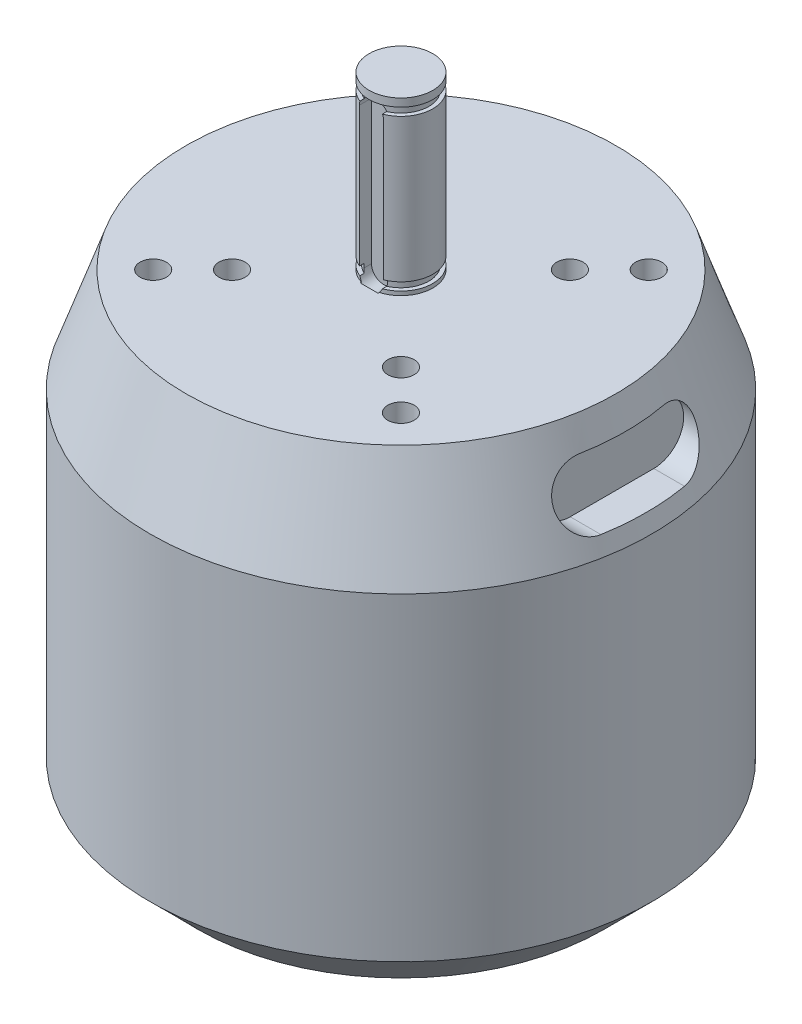
SolidWorks part; units mm, degrees
note: '?' marks a value the reader was unsure of.
ref_plane "정면" through (0, 0, 0) normal (0, 0, 1) x (1, 0, 0)
ref_plane "윗면" through (0, 0, 0) normal (0, 1, 0) x (1, 0, 0)
ref_plane "우측면" through (0, 0, 0) normal (1, 0, 0) x (0, 0, -1)
sketch "스케치1" plane through (0, 0, 0) normal (0, 0, 1) x (1, 0, 0)
  line L0 (0, 0) -> (0, 80.5) construction
  line L1 (0, 80.5) -> (4, 80.5)
  line L2 (4, 80.5) -> (4, 59)
  line L3 (4, 59) -> (31.5, 59)
  line L4 (31.5, 59) -> (31.5, 0)
  line L5 (31.5, 0) -> (0, 0)
  line L6 (0, 0) -> (0, 80.5)
  dimension "D1" = 63
  dimension "D2" = 59
  dimension "D3" = 8
  dimension "D4" = 21.5
revolve "회전1" add sketch "스케치1" angle 360 about L0
hole_wizard "M4x0.7 나사 구멍1" positions "스케치4" profile "스케치5" tap size "M4x0.7" standard "Ansi Metric"
sketch "스케치4" plane through (0, 59, 0) normal (0, 1, 0) x (1, 0, 0)
  circle A0 centre (0, 0) radius 15 construction
  circle A2 centre (0, 0) radius 22 construction
  point P0 (10.6066, 10.6066)
  point P2 (15.5563, 15.5563)
  point P20 (10.6066, -10.6066)
  point P21 (15.5563, -15.5563)
  point P22 (-10.6066, -10.6066)
  point P23 (-15.5563, -15.5563)
  point P24 (-10.6066, 10.6066)
  point P25 (-15.5563, 15.5563)
  point P26 (0, 0)
  dimension "D1" = 30
  dimension "D2" = 44
  dimension "D3" = 4
sketch "스케치5" plane through (10.6066, 59, -10.6066) normal (1, 0, 0) x (0, 0, 1)
  line L0 (0, 0) -> (0, 12.4914)
  line L1 (0, 12.4914) -> (1.65, 11.5)
  line L2 (1.65, 11.5) -> (1.65, 0)
  line L5 (1.65, 0) -> (0, 0)
  line L10 (0, 12.4914) -> (-1.65, 11.5) construction
  line L11 (0, -6.35) -> (0, 107.95) construction
  dimension "탭 드릴 지름" = 3.3
  dimension "탭 드릴 깊이" = 11.5
  dimension "드릴 각도" = 118
cosmetic thread "구멍 나사산1" parameters "D1"=8, "D2"=4
cosmetic thread "구멍 나사산2" parameters "D1"=8, "D2"=4
cosmetic thread "구멍 나사산3" parameters "D1"=8, "D2"=4
cosmetic thread "구멍 나사산4" parameters "D1"=8, "D2"=4
cosmetic thread "구멍 나사산5" parameters "D1"=8, "D2"=4
cosmetic thread "구멍 나사산6" parameters "D1"=8, "D2"=4
cosmetic thread "구멍 나사산7" parameters "D1"=8, "D2"=4
cosmetic thread "구멍 나사산8" parameters "D1"=8, "D2"=4
sketch "Sketch2" plane through (-5.6914, 80.5, 0.7546) normal (0, 1, 0) x (-1, 0, 0)
  line L0 (-5.6914, 3.2454) -> (-5.6914, -0.7546) construction
  line L1 (-5.6914, -0.7546) -> (-5.6914, 3.2454) construction
  circle A0 centre (-5.6914, -0.7546) radius 4 construction
  circle A2 centre (-5.6914, -0.7546) radius 4
  dimension "Angle from vertical" = 360
ref_plane "Plane1" through (0, 80.5, 4) normal (0, 0, -1) x (-1, 0, 0)
sketch "Sketch3" plane through (2.8457, 80.5, 4) normal (0, 0, -1) x (0, 1, 0)
  line L0 (-2.5, -2.8457) -> (-20.5, -2.8457) construction
  line L1 (-2.5, -1.3457) -> (-20.5, -1.3457)
  line L2 (-2.5, -4.3457) -> (-20.5, -4.3457)
  arc A0 (-2.5, -1.3457) -> (-2.5, -4.3457) centre (-2.5, -2.8457) cw
  arc A1 (-20.5, -1.3457) -> (-20.5, -4.3457) centre (-20.5, -2.8457) ccw
  dimension "Keyway width" = 3
  dimension "Distance from end face" = 2.5
  dimension "Length of slot" = 18
extrude "Cut-Extrude1" cut sketch "Sketch3" along normal blind 1.8
other "keyway (bs 4235 - part i)<1>"
chamfer "모따기1" distance 4.5 distance2 13 1 edges at (0, 59, -31.5)
chamfer "모따기2" distance 6 1 edges at (0, 0, -31.5)
sketch "스케치6" plane through (0, 0, 0) normal (0, -1, 0) x (1, 0, 0)
  circle A0 centre (0, 0) radius 7.5
  dimension "D1" = 15
extrude "보스-돌출1" add sketch "스케치6" along normal blind 2
sketch "스케치7" plane through (0, 0, 0) normal (1, 0, 0) x (0, 0, -1)
  line L0 (0, 0) -> (0, 80.5) construction
  line L1 (4, 80.5) -> (-4, 80.5) construction
  line L3 (4, 79.5) -> (3.5, 79.5)
  line L4 (4, 79.5) -> (4, 78.5)
  line L5 (4, 78.5) -> (3.5, 78.5)
  line L6 (3.5, 79.5) -> (3.5, 78.5)
  line L7 (4, 59) -> (4, 80.5) construction
  line L9 (4, 60.5) -> (3.5, 60.5)
  line L10 (4, 60.5) -> (4, 59.5)
  line L11 (4, 59.5) -> (3.5, 59.5)
  line L12 (3.5, 60.5) -> (3.5, 59.5)
  dimension "D1" = 1
  dimension "D2" = 1
  dimension "D3" = 0.5
  dimension "D4" = 20
revolve "컷-회전1" cut sketch "스케치7" angle 360 about L0
sketch "스케치9" plane through (0, 0, 0) normal (1, 0, 0) x (0, 0, -1)
  line L0 (5.25, 51.75) -> (-5.25, 51.75) construction
  line L1 (5.25, 48) -> (-5.25, 48)
  line L2 (5.25, 55.5) -> (-5.25, 55.5)
  line L4 (27, 59) -> (-27, 59) construction
  arc A0 (5.25, 48) -> (5.25, 55.5) centre (5.25, 51.75) ccw
  arc A1 (-5.25, 55.5) -> (-5.25, 48) centre (-5.25, 51.75) ccw
  point P2 (0, 51.75)
  dimension "D1" = 18
  dimension "D2" = 7.5
  dimension "D3" = 3.5
ref_plane "평면1" through (31.5, 0, 0) normal (1, 0, 0) x (0, 0, -1)
extrude "컷-돌출1" cut sketch "스케치9" against normal blind 5 from surface at 31.5 starting at plane "평면1"
sketch "스케치10" plane through (26.5, 0, 0) normal (1, 0, 0) x (0, 0, -1)
  line L0 (-9, 51.75) -> (9, 51.75) construction
  line L1 (0, 55.5) -> (0, 48) construction
  line L4 (-5.25, 55.5) -> (5.25, 55.5) construction
  line L5 (5.25, 48) -> (-5.25, 48) construction
  arc A0 (-5.25, 55.5) -> (-5.25, 48) centre (-5.25, 51.75) ccw construction
  arc A1 (5.25, 48) -> (5.25, 55.5) centre (5.25, 51.75) ccw construction
  point P14 (-6, 51.75)
  point P17 (-2, 51.75)
  point P18 (2, 51.75)
  point P19 (6, 51.75)
  dimension "D2" = 4
  dimension "D1" = 4
other "Phase1" parameters "지름"=4.2, "스터브길이"=5
ref_axis "기준축2" through (36.5, 51.75, -6) along (-1, 0, 0)?
other "Phase2" parameters "지름"=4.2, "스터브길이"=5.85
ref_axis "기준축3" through (36.5, 51.75, -2) along (-1, 0, 0)?
other "Phase3" parameters "지름"=4.2, "스터브길이"=5.85
ref_axis "기준축4" through (36.5, 51.75, 2) along (-1, 0, 0)?
other "sensor" parameters "지름"=4.2, "스터브길이"=5
ref_axis "기준축1" through (36.5, 51.75, 6) along (-1, 0, 0)?
